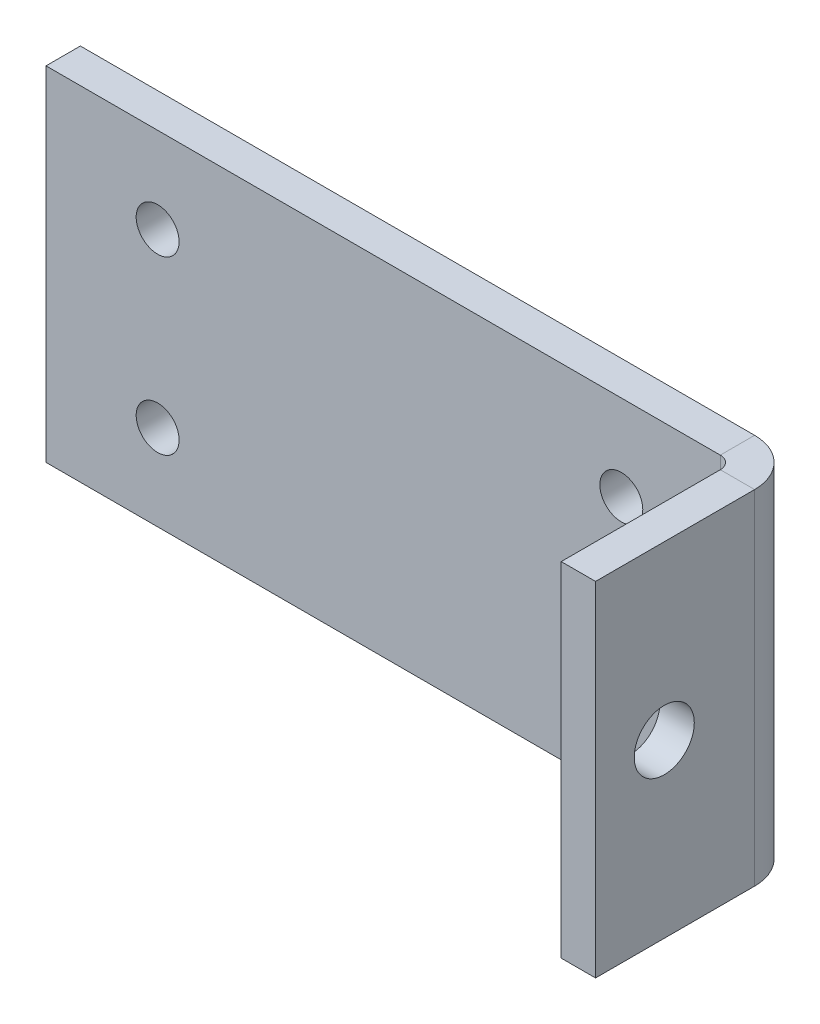
SolidWorks part; units mm, degrees
note: The reader was unsure of these and kept them because the rebuilt part matched: flange length of "邊線-凸緣1".
ref_plane "前基準面" through (0, 0, 0) normal (0, 0, 1) x (1, 0, 0)
ref_plane "上基準面" through (0, 0, 0) normal (0, 1, 0) x (1, 0, 0)
ref_plane "右基準面" through (0, 0, 0) normal (1, 0, 0) x (0, 0, -1)
sketch "草圖1" plane through (0, 0, 0) normal (0, 0, 1) x (1, 0, 0)
  line L0 (0, 10) -> (0, -10) construction
  line L1 (-20, 10) -> (20, 10)
  line L2 (-20, 10) -> (-20, -10)
  line L3 (-20, -10) -> (20, -10)
  line L4 (20, 10) -> (20, -10)
  dimension "D1" = 20
  dimension "D2" = 40
base flange "基材-凸緣1" sketch "草圖1" thickness 2 reverse thickness direction no parameters "D1"=0.7366
edge flange "邊線-凸緣1" sketch "草圖10" flange angle 90 flange length 12 flange position material outside bend radius 0.7366 thickness 2 relief rectangular parameters "D6"=10
sketch "草圖10" plane through (20, 0, 0) normal (1, 0, 0) x (0, 1, 0)
  line L0 (-10, 0) -> (10, 0) construction
  line L1 (-10, 0) -> (10, 0)
  line L2 (-10, 0) -> (-10, 10)
  line L3 (-10, 10) -> (10, 10)
  line L4 (10, 10) -> (10, 0)
bend "邊線彎折1" bend radius 0.7366 bend angle 90 parameters "D5"=1
hole_wizard "M3 螺紋孔2" positions "草圖12" profile "草圖11" tap size "M3" standard "ISO" end condition through all
sketch "草圖12" plane through (0, 0, 0) normal (0, 0, 1) x (1, 0, 0)
  line L1 (-20, 10) -> (-20, -10) construction
  line L2 (-20, -10) -> (19.2634, -10) construction
  line L3 (-20, 0) -> (22, 0) construction
  line L4 (-20, 10) -> (-20, -10) construction
  line L5 (22, 10) -> (22, -10) construction
  point P0 (-13.5, -5)
  point P3 (13.5, -5)
  point P21 (13.5, 5)
  point P22 (-13.5, 5)
  dimension "D1" = 5
  dimension "D2" = 27
  dimension "D3" = 6.5
sketch "草圖11" plane through (-13.5, -5, 0) normal (1, 0, 0) x (0, -1, 0)
  line L0 (0, 0) -> (0, 2)
  line L1 (0, 2) -> (1.25, 2)
  line L2 (1.25, 2) -> (1.25, 0)
  line L5 (1.25, 0) -> (0, 0)
  line L11 (0, -6.35) -> (0, 107.95) construction
  dimension "貫穿螺孔鑽直徑" = 2.5
  dimension "貫穿螺孔鑽深度" = 2
hole_wizard "Ø3.5 (3.5) 直徑孔2" positions "草圖14" profile "草圖13" hole size "Ø3.5" standard "JIS" end condition through all
sketch "草圖14" plane through (22, 0, 0) normal (1, 0, 0) x (0, 0, -1)
  line L3 (2, 10) -> (2, -10) construction
  point P0 (-6, 0)
  dimension "D1" = 8
sketch "草圖13" plane through (22, 0, 6) normal (0, 1, 0) x (0, 0, -1)
  line L0 (0, 0) -> (0, 42)
  line L1 (0, 42) -> (1.75, 42)
  line L2 (1.75, 42) -> (1.75, 0)
  line L5 (1.75, 0) -> (0, 0)
  line L11 (0, -6.35) -> (0, 107.95) construction
  dimension "貫穿孔直徑" = 3.5
  dimension "貫穿孔深度" = 42
sketch "彎折-線1" plane through (0, 0, 0) normal (0, 1, 0) x (1, 0, 0)
sketch "邊界方塊1" plane through (0, 0, 0) normal (0, 1, 0) x (1, 0, 0)
sheet metal parameters "鈑金3" thickness 2 parameters "D1"=0.7366
flat pattern "平板-型式3" [suppressed]
sketch "彎折-線2" plane through (0, 0, 0) normal (0, 1, 0) x (1, 0, 0)
sketch "邊界方塊2" [suppressed] plane through (0, 0, 0) normal (0, 1, 0) x (1, 0, 0)
sheet metal parameters "鈑金4" thickness 2 parameters "D1"=0.7366
flat pattern "平板-型式3" [suppressed]
sketch "彎折-線2" plane through (0, 0, 0) normal (0, 1, 0) x (1, 0, 0)
sketch "邊界方塊2" [suppressed] plane through (0, 0, 0) normal (0, 1, 0) x (1, 0, 0)
bend of the flat pattern "平板-<邊線彎折1>1"
sheet metal parameters "鈑金5" thickness 2 parameters "D1"=0.7366
flat pattern "平板-型式3" [suppressed]
sketch "彎折-線2" plane through (0, 0, 0) normal (0, 1, 0) x (1, 0, 0)
sketch "邊界方塊2" [suppressed] plane through (0, 0, 0) normal (0, 1, 0) x (1, 0, 0)
bend of the flat pattern "平板-<邊線彎折1>1"
sheet metal parameters "鈑金6" thickness 2 parameters "D1"=0.7366
flat pattern "平板-型式3" [suppressed]
sketch "彎折-線2" plane through (0, 0, 0) normal (0, 1, 0) x (1, 0, 0)
sketch "邊界方塊2" [suppressed] plane through (0, 0, 0) normal (0, 1, 0) x (1, 0, 0)
bend of the flat pattern "平板-<邊線彎折1>1"
